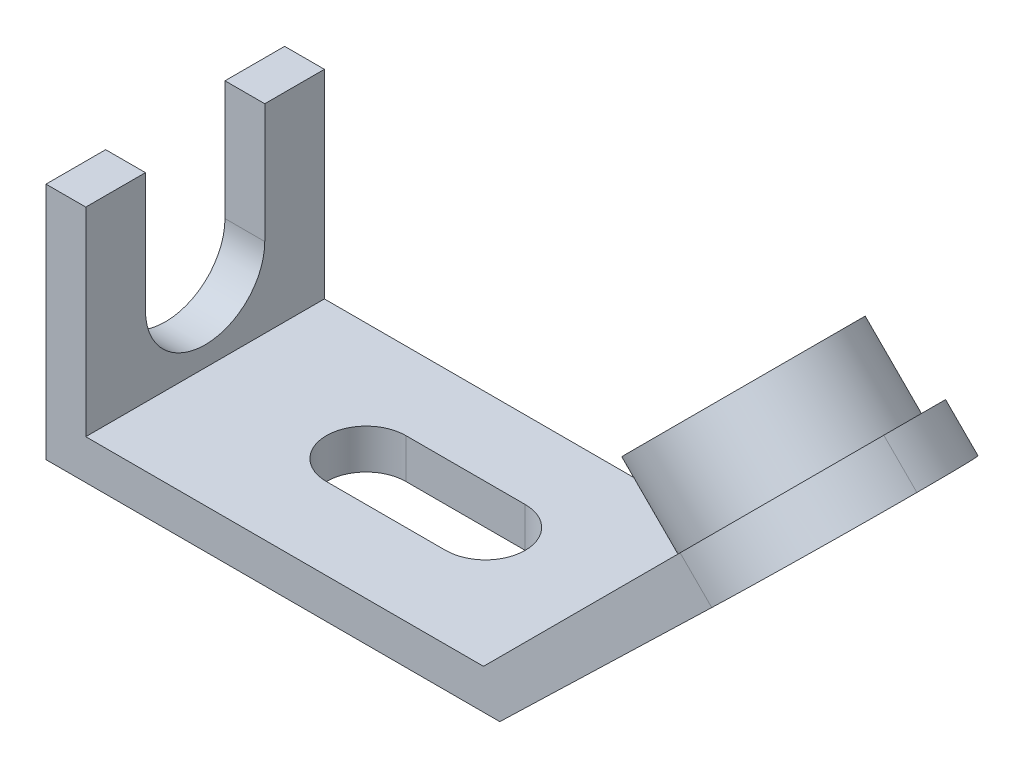
SolidWorks part; units mm, degrees
ref_plane "Front Plane" through (0, 0, 0) normal (0, 0, 1) x (1, 0, 0)
ref_plane "Top Plane" through (0, 0, 0) normal (0, 1, 0) x (1, 0, 0)
ref_plane "Right Plane" through (0, 0, 0) normal (1, 0, 0) x (0, 0, -1)
sketch "Sketch1" plane through (0, 0, 0) normal (0, 0, 1) x (1, 0, 0)
  line L0 (0, 0) -> (0, 74125.2094) construction
  line L1 (0, 0) -> (74125.2094, 0) construction
  line L2 (0, 0) -> (0, 60)
  line L3 (0, 60) -> (10, 60)
  line L4 (10, 60) -> (10, 10)
  line L5 (10, 10) -> (110, 10)
  line L6 (110, 10) -> (180.649, 80.649)
  line L7 (180.649, 80.649) -> (188.9629, 72.335)
  line L8 (188.9629, 72.335) -> (114.1, 0)
  line L9 (114.1, 0) -> (0, 0)
  dimension "D1" = 60
  dimension "D2" = 10
  dimension "D3" = 50
  dimension "D4" = 100
  dimension "D5" = 114.1
  dimension "D6" = 135
  dimension "D7" = 135.984
  dimension "D8" = 104.1
extrude "Boss-Extrude1" add sketch "Sketch1" along normal blind 60
sketch "Sketch2" plane through (50, -50, 0) normal (-0.7071, 0.7071, 0) x (0, 0, 1)
  line L0 (0, 184.7655) -> (60, 84.8528) construction
  line L1 (60, 184.7655) -> (0, 84.8528) construction
  line L2 (60, 84.8528) -> (0, 84.8528) construction
  line L3 (0, 184.7655) -> (0, 84.8528) construction
  circle A0 centre (30, 154.8528) radius 15
  circle A1 centre (30, 154.8528) radius 25
  dimension "D2" = 50
  dimension "D3" = 30
  dimension "D1" = 70
  dimension "D4" = 30
extrude "Boss-Extrude2" add sketch "Sketch2" along normal blind 20
fillet "Fillet1" radius 30 2 edges at (184.8059, 76.492, 60) (184.8059, 76.492, 0)
sketch "Sketch3" plane through (0, 10, 0) normal (0, 1, 0) x (1, 0, 0)
  line L0 (50, -29.5146) -> (80, -29.5146) construction
  line L1 (50, -19.5146) -> (80, -19.5146)
  line L2 (50, -39.5146) -> (80, -39.5146)
  line L3 (110, -60) -> (110, 0) construction
  arc A0 (50, -19.5146) -> (50, -39.5146) centre (50, -29.5146) ccw
  arc A1 (80, -39.5146) -> (80, -19.5146) centre (80, -29.5146) ccw
  point P2 (65, -29.5146)
  dimension "D3" = 10
  dimension "D1" = 30
  dimension "D2" = 30
extrude "Cut-Extrude1" cut sketch "Sketch3" against normal blind 20
sketch "Sketch5" plane through (0, 0, 0) normal (-1, 0, 0) x (0, 0, 1)
  line L0 (30, 30) -> (30, 130) construction
  line L1 (15, 30) -> (15, 130)
  line L2 (45, 30) -> (45, 130)
  line L3 (60, 0) -> (0, 0) construction
  line L4 (0, 60) -> (0, 0) construction
  arc A0 (15, 30) -> (45, 30) centre (30, 30) ccw
  arc A1 (45, 130) -> (15, 130) centre (30, 130) ccw
  point P2 (30, 80)
  dimension "D4" = 15
  dimension "D1" = 100
  dimension "D2" = 30
  dimension "D3" = 30
extrude "Cut-Extrude2" cut sketch "Sketch5" against normal blind 20
sketch "Sketch6" plane through (50, -50, 0) normal (-0.7071, 0.7071, 0) x (0, 0, 1)
  circle A0 centre (30, 154.8528) radius 15
extrude "Cut-Extrude3" cut sketch "Sketch6" against normal blind 14
